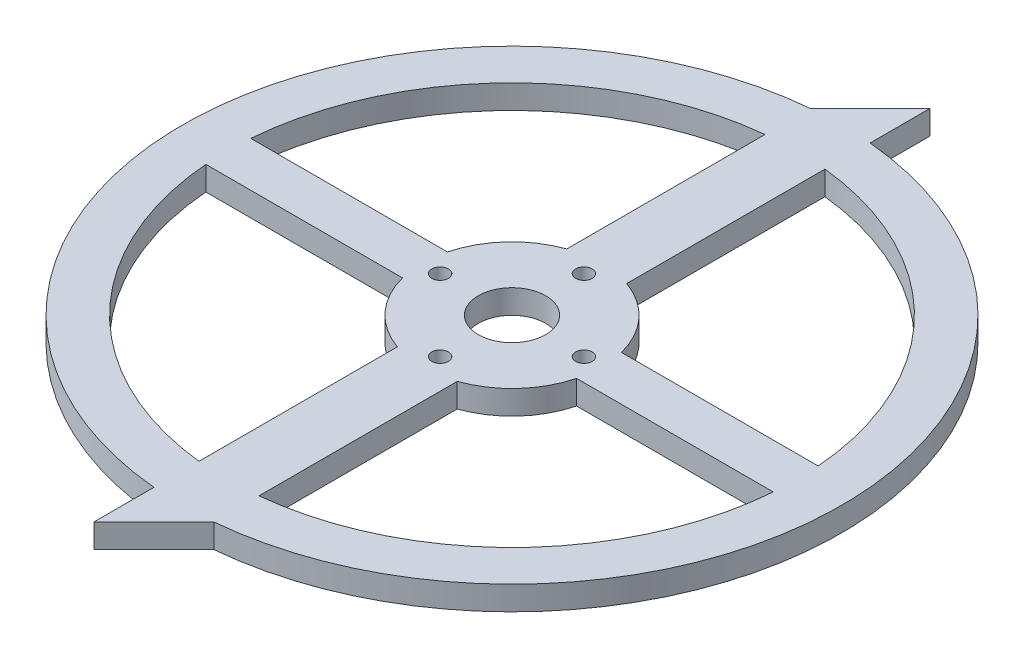
SolidWorks part; units mm, degrees
material "Alloy Steel"
ref_plane "Front Plane" through (0, 0, 0) normal (0, 0, 1) x (1, 0, 0)
ref_plane "Top Plane" through (0, 0, 0) normal (0, 1, 0) x (1, 0, 0)
ref_plane "Right Plane" through (0, 0, 0) normal (1, 0, 0) x (0, 0, -1)
sketch "Sketch1" plane through (0, 0, 0) normal (0, 1, 0) x (1, 0, 0)
  line L0 (-6.35, 17.9605) -> (-6.35, 59.9899)
  line L1 (6.35, 17.9605) -> (6.35, 59.9899)
  line L2 (-6.35, -17.9605) -> (-6.35, -59.9899)
  line L3 (6.35, -17.9605) -> (6.35, -59.9899)
  line L4 (6.35, -69.5608) -> (-6.35, -82.2608)
  line L5 (-6.35, -82.2608) -> (-6.35, -69.5608)
  line L6 (-6.35, 69.5608) -> (6.35, 82.2608)
  line L7 (6.35, 82.2608) -> (6.35, 69.5608)
  line L8 (-60.325, 0) -> (60.325, 0) construction
  line L9 (60.1367, 4.7625) -> (-60.1367, 4.7625)
  line L10 (60.1367, -4.7625) -> (-60.1367, -4.7625)
  line L12 (0, 60.325) -> (0, 19.05) construction
  circle A0 centre (0, 0) radius 69.85
  circle A1 centre (0, 0) radius 60.325
  circle A2 centre (0, 0) radius 19.05
  point P21 (0, 0)
  point P29 (0, 0)
  dimension "D1" = 139.7
  dimension "D2" = 120.65
  dimension "D3" = 38.1
  dimension "D4" = 12.7
  dimension "D6" = 12.7
  dimension "D7" = 9.525
  dimension "D5" = 2
extrude "Boss-Extrude1" add sketch "Sketch1" along normal blind 5.08 contours A0 A1 | A2 L2 A1 L3 | A0 L5 L4 | A2 L10 | A2 L9 A1 L10 | L10 A2 L9 | L9 A2 | A2 L10 A1 L9 | A2 L1 A1 L0 | A0 L7 L6 region at (0, 0, -39.4511) region at (0, 0, -10.7134) region at (-39.5556, 0, 0) region at (0, 0, 0) region at (39.5556, 0, 0) region at (0, 0, 10.7134) region at (0, 0, 39.4511) region at (-2.183, 0, 73.9231) region at (0, 0, 67.8743) region at (2.183, 0, -73.9231)
sketch "Sketch2" plane through (0, 5.08, 0) normal (0, 1, 0) x (1, 0, 0)
  circle A0 centre (0, 0) radius 7.1438
  circle A1 centre (-15.24, 0) radius 1.7526
  circle A2 centre (0, 15.24) radius 1.7526
  circle A3 centre (15.24, 0) radius 1.7526
  circle A4 centre (0, -15.24) radius 1.7526
  point P14 (0, 0)
  dimension "D1" = 14.2875
  dimension "D2" = 3.5052
  dimension "D3" = 15.24
  dimension "D4" = 4
extrude "Cut-Extrude1" cut sketch "Sketch2" against normal blind 6.35
